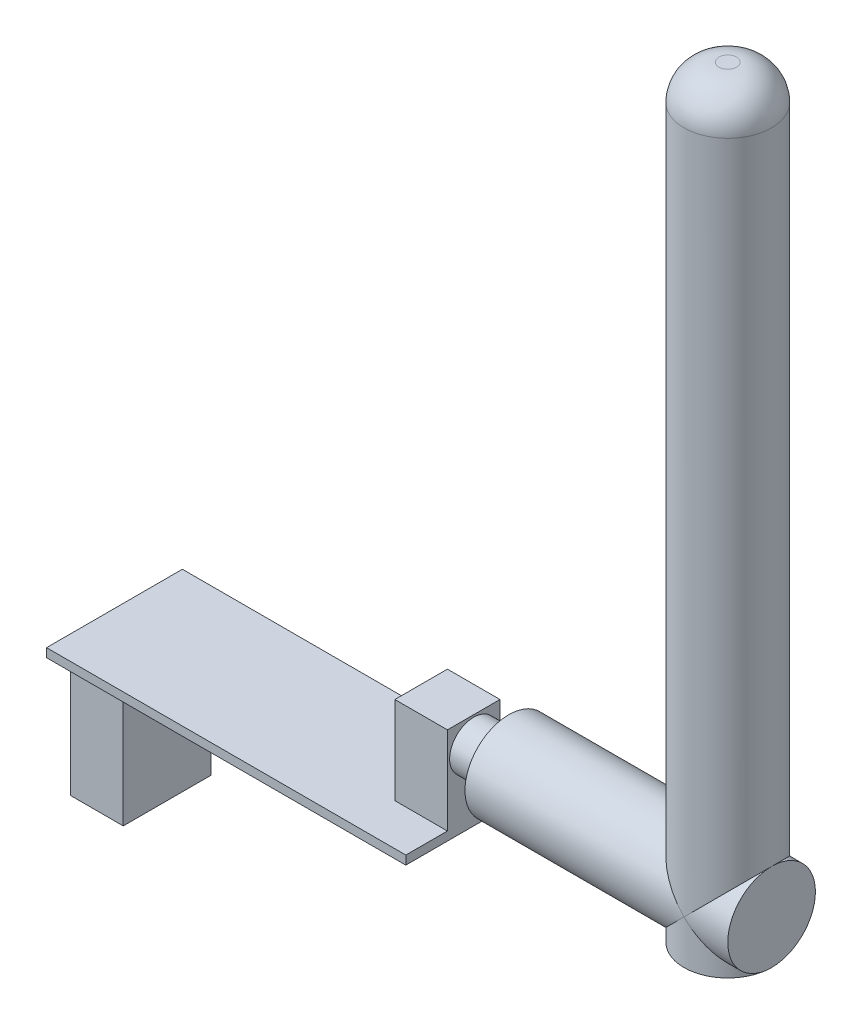
SolidWorks part; units mm, degrees
ref_plane "Спереди" through (0, 0, 0) normal (0, 0, 1) x (1, 0, 0)
ref_plane "Сверху" through (0, 0, 0) normal (0, 1, 0) x (1, 0, 0)
ref_plane "Справа" through (0, 0, 0) normal (1, 0, 0) x (0, 0, -1)
sketch "Эскиз1" plane through (0, 0, 0) normal (0, 1, 0) x (1, 0, 0)
  line L1 (-20.5, 7.75) -> (20.5, 7.75)
  line L2 (-20.5, 7.75) -> (-20.5, -7.75)
  line L3 (-20.5, -7.75) -> (20.5, -7.75)
  line L4 (20.5, 7.75) -> (20.5, -7.75)
  line L5 (-20.5, 7.75) -> (20.5, -7.75) construction
  line L6 (-20.5, -7.75) -> (20.5, 7.75) construction
  point P0 (0, 0)
  dimension "D1" = 15.5
  dimension "D2" = 41
base flange "Базовая кромка1" sketch "Эскиз1" thickness 1 reverse thickness direction no parameters "D1"=1
sketch "Эскиз6" plane through (0, 0, 0) normal (0, 1, 0) x (1, 0, 0)
  line L0 (20.5, -7.75) -> (20.5, 7.75) construction
  line L1 (14.5, 3) -> (20.5, 3)
  line L2 (14.5, 3) -> (14.5, -3)
  line L3 (14.5, -3) -> (20.5, -3)
  line L4 (20.5, 3) -> (20.5, -3)
  line L5 (14.5, 3) -> (20.5, -3) construction
  line L6 (14.5, -3) -> (20.5, 3) construction
  point P0 (17.5, 0)
  point P5 (20.5, 0)
  point P8 (20.5, 0)
  dimension "D1" = 6
extrude "Бобышка-Вытянуть1" add sketch "Эскиз6" along normal blind 10
sketch "Эскиз7" plane through (20.5, 0, 0) normal (1, 0, 0) x (0, 0, -1)
  line L0 (-3, 10) -> (0, 7) construction
  line L1 (0, 7) -> (3, 10) construction
  circle A0 centre (0, 7) radius 2.75
  dimension "D1" = 5.5
extrude "Бобышка-Вытянуть2" add sketch "Эскиз7" along normal blind 4
sketch "Эскиз8" plane through (24.5, 0, 0) normal (1, 0, 0) x (0, 0, -1)
  circle A0 centre (0, 7) radius 5
  circle A1 centre (0, 7) radius 2.75 construction
  dimension "D1" = 10
extrude "Бобышка-Вытянуть3" add sketch "Эскиз8" along normal blind 30
ref_plane "Плоскость1" through (0, 2, 0) normal (0, -1, 0) x (-1, 0, 0)
sketch "Эскиз9" plane through (0, 2, 0) normal (0, -1, 0) x (-1, 0, 0)
  line L0 (-54.5, 5) -> (-54.5, -5) construction
  line L1 (-54.5, -5) -> (-24.5, -5) construction
  line L3 (0, 0) -> (-49.5, 0) construction
  circle A0 centre (-49.5, 0) radius 5
extrude "Бобышка-Вытянуть4" add sketch "Эскиз9" against normal blind 87
fillet "Скругление1" radius 4 1 edges at (49.5, 89, -5)
sketch "Эскиз10" plane through (0, -1, 0) normal (0, -1, 0) x (1, 0, 0)
  line L0 (-20.5, -7.75) -> (-20.5, 7.75) construction
  line L1 (-20.5, 5) -> (-14.5, 5)
  line L2 (-20.5, 5) -> (-20.5, -5)
  line L3 (-20.5, -5) -> (-14.5, -5)
  line L4 (-14.5, 5) -> (-14.5, -5)
  line L5 (-20.5, 5) -> (-14.5, -5) construction
  line L6 (-20.5, -5) -> (-14.5, 5) construction
  point P0 (-17.5, 0)
  point P7 (-20.5, 0)
  point P8 (-20.5, 0)
  dimension "D1" = 6
  dimension "D2" = 10
extrude "Бобышка-Вытянуть5" add sketch "Эскиз10" along normal blind 15
sketch "Сгиб-Линии1" plane through (0, 0, 0) normal (0, 1, 0) x (1, 0, 0)
sketch "Граничная рамка1" plane through (0, 0, 0) normal (0, 1, 0) x (1, 0, 0)
sheet metal parameters "Листовой металл3" thickness 1 parameters "D1"=1
flat pattern "Развертка3" [suppressed]
sketch "Сгиб-Линии2" plane through (0, 0, 0) normal (0, 1, 0) x (1, 0, 0)
sketch "Граничная рамка2" [suppressed] plane through (0, 0, 0) normal (0, 1, 0) x (1, 0, 0)
sheet metal parameters "Листовой металл4" thickness 1 parameters "D1"=1
flat pattern "Развертка3"
sketch "Сгиб-Линии2" plane through (0, 0, 0) normal (0, 1, 0) x (1, 0, 0)
sketch "Граничная рамка2" [suppressed] plane through (0, 0, 0) normal (0, 1, 0) x (1, 0, 0)
sheet metal parameters "Листовой металл5" thickness 1 parameters "D1"=1
flat pattern "Развертка3"
sketch "Сгиб-Линии2" plane through (0, 0, 0) normal (0, 1, 0) x (1, 0, 0)
sketch "Граничная рамка2" [suppressed] plane through (0, 0, 0) normal (0, 1, 0) x (1, 0, 0)
sheet metal parameters "Листовой металл6" thickness 1 parameters "D1"=1
flat pattern "Развертка3"
sketch "Сгиб-Линии2" plane through (0, 0, 0) normal (0, 1, 0) x (1, 0, 0)
sketch "Граничная рамка2" [suppressed] plane through (0, 0, 0) normal (0, 1, 0) x (1, 0, 0)
sheet metal parameters "Листовой металл7" thickness 1 parameters "D1"=1
flat pattern "Развертка3"
sketch "Сгиб-Линии2" plane through (0, 0, 0) normal (0, 1, 0) x (1, 0, 0)
sketch "Граничная рамка2" [suppressed] plane through (0, 0, 0) normal (0, 1, 0) x (1, 0, 0)
sheet metal parameters "Листовой металл8" thickness 1 parameters "D1"=1
flat pattern "Развертка3"
sketch "Сгиб-Линии2" plane through (0, 0, 0) normal (0, 1, 0) x (1, 0, 0)
sketch "Граничная рамка2" [suppressed] plane through (0, 0, 0) normal (0, 1, 0) x (1, 0, 0)
